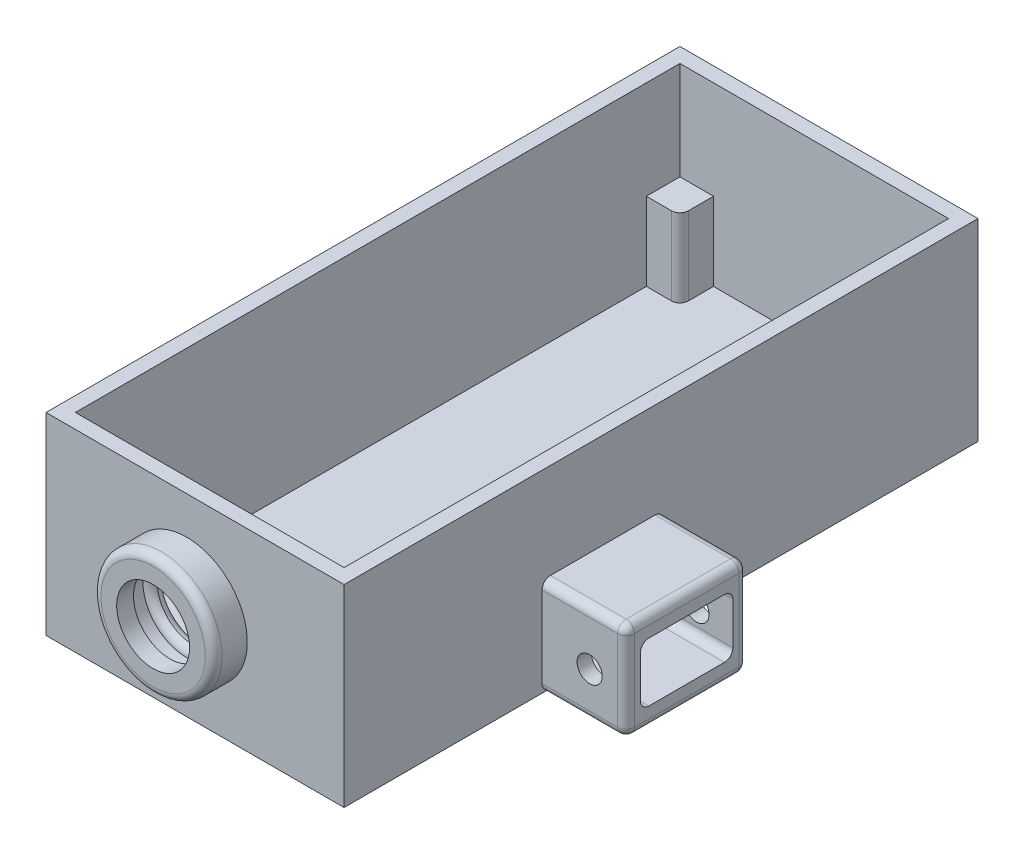
SolidWorks part; units mm, degrees
ref_plane "Front Plane" through (0, 0, 0) normal (0, 0, 1) x (1, 0, 0)
ref_plane "Top Plane" through (0, 0, 0) normal (0, 1, 0) x (1, 0, 0)
ref_plane "Right Plane" through (0, 0, 0) normal (1, 0, 0) x (0, 0, -1)
sketch "Sketch1" plane through (0, 0, 0) normal (0, 1, 0) x (1, 0, 0)
  line L1 (0, 0) -> (35.5, 0)
  line L2 (0, 0) -> (0, 75.5)
  line L3 (0, 75.5) -> (35.5, 75.5)
  line L4 (35.5, 0) -> (35.5, 75.5)
  dimension "D1" = 75.5
  dimension "D2" = 35.5
extrude "Boss-Extrude2" add sketch "Sketch1" along normal blind 23
sketch3d "3DSketch1"
  line L0 (33.75, 23, -1.75) -> (33.75, 23, -73.75)
  line L1 (33.75, 23, -73.75) -> (1.75, 23, -73.75)
  line L2 (1.75, 23, -73.75) -> (1.75, 23, -1.75)
  line L3 (1.75, 23, -1.75) -> (33.75, 23, -1.75)
  line L4 (33.75, 23, -1.75) -> (33.75, 23, -73.75)
  line L5 (33.75, 23, -73.75) -> (1.75, 23, -73.75)
  line L6 (1.75, 23, -73.75) -> (1.75, 23, -1.75)
  line L7 (1.75, 23, -1.75) -> (33.75, 23, -1.75)
  dimension "D1" = 1.75
extrude "Cut-Extrude1" cut sketch "3DSketch1" along direction (0, -1, 0) on the side against the normal blind 21
sketch "Sketch2" plane through (0, 2, 0) normal (0, 1, 0) x (1, 0, 0)
  line L0 (1.75, 37.75) -> (33.75, 37.75) construction
  line L1 (1.75, 73.75) -> (5.75, 73.75)
  line L2 (1.75, 73.75) -> (1.75, 69.75)
  line L3 (1.75, 69.75) -> (5.75, 69.75)
  line L4 (5.75, 73.75) -> (5.75, 69.75)
  line L5 (33.75, 73.75) -> (29.75, 73.75)
  line L6 (33.75, 73.75) -> (33.75, 69.75)
  line L7 (33.75, 69.75) -> (29.75, 69.75)
  line L8 (29.75, 73.75) -> (29.75, 69.75)
  line L9 (1.75, 73.75) -> (1.75, 1.75) construction
  line L10 (33.75, 1.75) -> (33.75, 73.75) construction
  line L11 (33.75, 5.75) -> (29.75, 5.75)
  line L12 (29.75, 1.75) -> (29.75, 5.75)
  line L13 (33.75, 1.75) -> (29.75, 1.75)
  line L14 (33.75, 1.75) -> (33.75, 5.75)
  line L15 (1.75, 5.75) -> (5.75, 5.75)
  line L16 (5.75, 1.75) -> (5.75, 5.75)
  line L17 (1.75, 1.75) -> (5.75, 1.75)
  line L18 (1.75, 1.75) -> (1.75, 5.75)
  dimension "D1" = 4
  dimension "D2" = 4
  dimension "D3" = 4
  dimension "D4" = 4
extrude "Boss-Extrude3" add sketch "Sketch2" along normal blind 9.3
sketch "Sketch3" plane through (0, 23, 0) normal (0, 1, 0) x (1, 0, 0)
  line L0 (35.5, 0) -> (35.5, 26.3) construction
  line L1 (35.5, 0) -> (35.5, 75.5) construction
  line L2 (35.5, 26.3) -> (35.5, 35.3) construction
  line L4 (35.5, 35.3) -> (32.25, 35.3)
  line L5 (35.5, 35.3) -> (35.5, 26.3)
  line L6 (35.5, 26.3) -> (32.25, 26.3)
  line L7 (32.25, 35.3) -> (32.25, 26.3)
  dimension "D1" = 26.3
  dimension "D2" = 9
extrude "Cut-Extrude2" cut sketch "Sketch3" against normal blind 4.25 from offset 15.05 offset against normal yes
sketch "Sketch6" plane through (0, 0, 0) normal (0, 0, 1) x (1, 0, 0)
  line L0 (1.75, 11.3) -> (5.75, 11.3) construction
  circle A0 centre (16.7584, 11.3) radius 4.25
extrude "Cut-Extrude4" cut sketch "Sketch6" against normal up to vertex (1.75 mm away)
fillet "Fillet1" radius 1 1 edges at (21.0084, 11.3, -1.75)
fillet "Fillet2" radius 1 1 edges at (21.0084, 11.3, 0)
sketch "Sketch7" plane through (0, 0, 0) normal (0, 0, 1) x (1, 0, 0)
  circle A0 centre (16.7584, 11.3) radius 5.2182
  circle A1 centre (16.7584, 11.3) radius 7.2182
  dimension "D1" = 2
extrude "Boss-Extrude4" add sketch "Sketch7" along normal blind 2
sketch "Sketch9" plane through (0, 0, 2) normal (0, 0, 1) x (1, 0, 0)
  circle A0 centre (16.7584, 11.3) radius 7.2182
extrude "Boss-Extrude5" add sketch "Sketch9" along normal blind 2
fillet "Fillet4" radius 1 1 edges at (23.9766, 11.3, 4)
sketch "Sketch10" plane through (0, 0, 4) normal (0, 0, 1) x (1, 0, 0)
  circle A0 centre (16.7584, 11.3) radius 4.3409
extrude "Cut-Extrude5" cut sketch "Sketch10" against normal blind 2
fillet "Fillet5" radius 1 1 edges at (34.625, 3.7, -26.3)
fillet "Fillet6" radius 1 1 edges at (34.625, 3.7, -35.3)
fillet "Fillet7" radius 1 4 edges at (5.75, 6.65, -69.75) (5.75, 6.65, -5.75) (29.75, 6.65, -5.75) (29.75, 6.65, -69.75)
fillet "Fillet9" radius 1 2 edges at (34.625, 7.95, -35.3) (34.625, 7.95, -26.3)
sketch "Sketch12" plane through (35.5, 0, 0) normal (1, 0, 0) x (0, 0, -1)
  line L0 (35.3, 5.825) -> (26.3, 5.825) construction
  line L1 (35.3, 4.7) -> (35.3, 6.95) construction
  line L2 (26.3, 4.7) -> (26.3, 6.95) construction
  line L3 (0, 0) -> (75.5, 0) construction
  line L4 (35.3, 9.325) -> (26.3, 9.325)
  line L5 (36.3, 8.325) -> (36.3, 3.325)
  line L6 (35.3, 2.325) -> (26.3, 2.325)
  line L7 (25.3, 8.325) -> (25.3, 3.325)
  line L8 (36.3, 9.325) -> (25.3, 2.325) construction
  line L9 (36.3, 2.325) -> (25.3, 9.325) construction
  line L10 (37.0205, 11.65) -> (24.5795, 11.65)
  line L11 (38.0205, 10.65) -> (38.0205, 1)
  line L12 (37.0205, 0) -> (24.5795, 0)
  line L13 (23.5795, 10.65) -> (23.5795, 1)
  line L14 (38.0205, 11.65) -> (23.5795, 0) construction
  line L15 (38.0205, 0) -> (23.5795, 11.65) construction
  arc A0 (36.3, 3.325) -> (35.3, 2.325) centre (35.3, 3.325) cw
  arc A1 (35.3, 9.325) -> (36.3, 8.325) centre (35.3, 8.325) cw
  arc A2 (26.3, 9.325) -> (25.3, 8.325) centre (26.3, 8.325) ccw
  arc A3 (26.3, 2.325) -> (25.3, 3.325) centre (26.3, 3.325) cw
  arc A4 (24.5795, 0) -> (23.5795, 1) centre (24.5795, 1) cw
  arc A5 (24.5795, 11.65) -> (23.5795, 10.65) centre (24.5795, 10.65) ccw
  arc A6 (38.0205, 1) -> (37.0205, 0) centre (37.0205, 1) cw
  arc A7 (37.0205, 11.65) -> (38.0205, 10.65) centre (37.0205, 10.65) cw
  point P6 (30.8, 5.825)
  point P11 (30.8, 5.825)
  point P18 (0, 0)
  dimension "D3" = 1
  dimension "D1" = 7
  dimension "D2" = 11
extrude "Boss-Extrude7" add sketch "Sketch12" along normal blind 10
fillet "Fillet10" radius 1 8 edges at (45.5, 5.825, -23.5795) (45.5, 11.3571, -23.8724) (45.5, 11.65, -30.8) (45.5, 11.3571, -37.7276) (45.5, 5.825, -38.0205) (45.5, 0.2929, -37.7276) (45.5, 0, -30.8) (45.5, 0.2929, -23.8724)
sketch "Sketch13" plane through (0, 0, -23.5795) normal (0, 0, 1) x (1, 0, 0)
  line L0 (44.5, 1) -> (44.5, 10.65) construction
  circle A0 centre (41.17, 5.3198) radius 1.5
  dimension "D1" = 3.33
extrude "Cut-Extrude6" cut sketch "Sketch13" against normal blind 21
